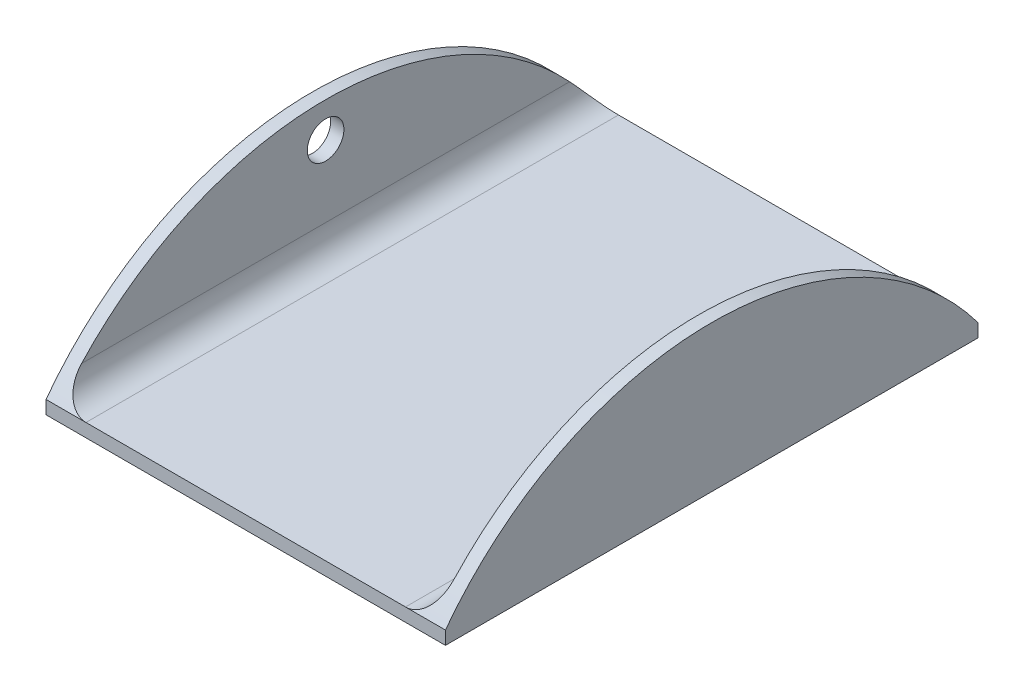
SolidWorks part; units mm, degrees
ref_plane "Front Plane" through (0, 0, 0) normal (0, 0, 1) x (1, 0, 0)
ref_plane "Top Plane" through (0, 0, 0) normal (0, 1, 0) x (1, 0, 0)
ref_plane "Right Plane" through (0, 0, 0) normal (1, 0, 0) x (0, 0, -1)
sketch "Sketch1" plane through (0, 0, 0) normal (0, 1, 0) x (1, 0, 0)
  line L1 (0, 0) -> (76.2, 0)
  line L2 (0, 0) -> (0, 101.6)
  line L3 (0, 101.6) -> (76.2, 101.6)
  line L4 (76.2, 0) -> (76.2, 101.6)
  dimension "D1" = 76.2
  dimension "D2" = 101.6
extrude "Base Extrude" add sketch "Sketch1" along normal blind 2.54
sketch "Sketch2" plane through (76.2, 0, 0) normal (1, 0, 0) x (0, 0, -1)
  line L2 (0, 2.54) -> (101.6, 2.54) construction
  line L3 (101.6, 2.54) -> (101.6, 0)
  line L4 (101.6, 0) -> (0, 0)
  line L5 (0, 0) -> (0, 2.54)
  arc A1 (0, 2.54) -> (101.6, 2.54) centre (50.8, -35.56) cw
  point P6 (50.8, 27.94)
  dimension "D1" = 25.4
extrude "Wall Extrude" add sketch "Sketch2" against normal blind 2.54 contours A1 L3 L4 L5
ref_plane "Wall Plane" through (38.1, 0, 0) normal (1, 0, 0) x (0, 0, -1)
mirror "Wall Mirror" about plane through (38.1, 0, 0) normal (1, 0, 0) of "Wall Extrude"
sketch "Sketch3" plane through (0, 0, 0) normal (-1, 0, 0) x (0, 0, 1)
  line L0 (-50.8, 27.94) -> (-50.8, -0.5285) construction
  circle A0 centre (-50.8, 21.2725) radius 3.4925
  arc A1 (0, 2.54) -> (-101.6, 2.54) centre (-50.8, -35.56) ccw construction
  point P8 (0, 0)
  point P9 (0, 0)
  dimension "D1" = 6.985
  dimension "D2" = 6.6675
extrude "Cut-Extrude1" cut sketch "Sketch3" against normal up to next
fillet "Fillet2" radius 5.08 2 edges at (2.54, 2.54, -50.8) (73.66, 2.54, -50.8)
